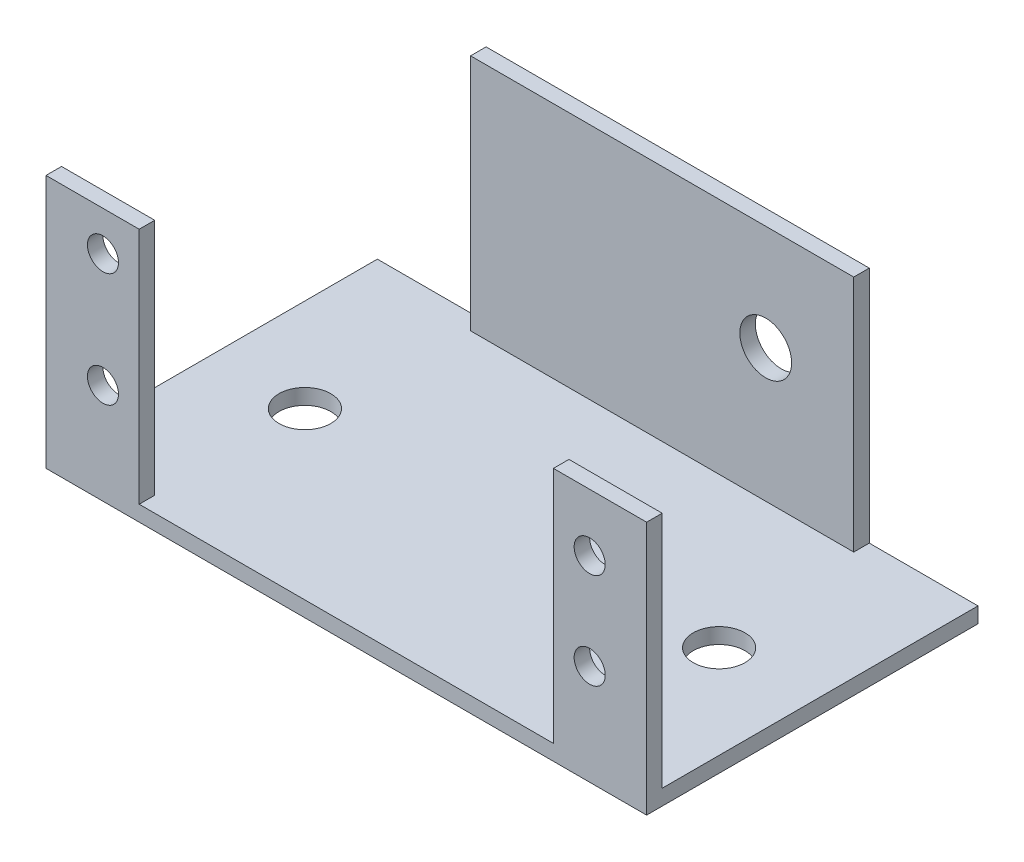
SolidWorks part; units mm, degrees
ref_plane "Front Plane" through (0, 0, 0) normal (0, 0, 1) x (1, 0, 0)
ref_plane "Top Plane" through (0, 0, 0) normal (0, 1, 0) x (1, 0, 0)
ref_plane "Right Plane" through (0, 0, 0) normal (1, 0, 0) x (0, 0, -1)
sketch "Sketch1" plane through (0, 0, 0) normal (0, 1, 0) x (1, 0, 0)
  line L0 (-29, -14.5) -> (29, -14.5)
  line L1 (29, 16) -> (-29, 16)
  line L2 (29, 16) -> (29, -16)
  line L3 (29, -16) -> (-29, -16)
  line L4 (-29, 16) -> (-29, -16)
  line L5 (29, 16) -> (-29, -16) construction
  line L6 (29, -16) -> (-29, 16) construction
  line L7 (-20, -14.5) -> (-20, -16)
  line L8 (20, -14.5) -> (20, -16)
  line L10 (18.5, 16) -> (-18.5, 16)
  line L11 (18.5, 16) -> (18.5, 14.5)
  line L12 (18.5, 14.5) -> (-18.5, 14.5)
  line L13 (-18.5, 16) -> (-18.5, 14.5)
  circle A0 centre (-20, 0) radius 2.5
  circle A1 centre (20, 0) radius 2.5
  point P0 (0, 0)
  point P16 (0, -14.5)
  point P21 (0, 14.5)
  point P22 (0, 0)
  dimension "D4" = 5
  dimension "D1" = 58
  dimension "D2" = 32
  dimension "D3" = 1.5
  dimension "D5" = 20
  dimension "D6" = 20
  dimension "D7" = 40
  dimension "D8" = 20
  dimension "D9" = 37
  dimension "D10" = 1.5
extrude "Boss-Extrude1" add sketch "Sketch1" against normal blind 1.5 contours L1 L4 L0 L2 A1 A0 | L0 L4 L3 L2 | L1 L13 L12 L11 | A0 | A1 | L2 L1 L4 L3 region at (0, 0, -0.2869) region at (0, 0, -15.25) region at (-20, 0, 0) region at (20, 0, 0)
extrude "Boss-Extrude2" add sketch "Sketch1<3>" along normal blind 23 contours L7 L0 L4 L3 | L0 L8 L3 L2 region at (-24.5, 0, 15.25) region at (24.5, 0, 15.25)
sketch "Sketch1<3>" plane through (0, 0, 0) normal (0, 1, 0) x (1, 0, 0) same geometry as "Sketch1"
sketch "Sketch2" plane through (0, 0, 16) normal (0, 0, 1) x (1, 0, 0)
  circle A0 centre (-23.5, 19.1975) radius 1.5
  circle A1 centre (-23.5, 8.1975) radius 1.5
  circle A2 centre (23.5, 17.4466) radius 1.5
  circle A3 centre (23.5, 8.1975) radius 1.5
  point P8 (0, 0)
  dimension "D4" = 3
  dimension "D1" = 11
  dimension "D2" = 47
  dimension "D3" = 23.5
extrude "Cut-Extrude1" cut sketch "Sketch2" against normal through all
extrude "Boss-Extrude3" add sketch "Sketch1<4>" along normal blind 23 contours L1 L13 L12 L11 region at (0, 0, -15.25)
sketch "Sketch1<4>" plane through (0, 0, 0) normal (0, 1, 0) x (1, 0, 0) same geometry as "Sketch1"
sketch "Sketch3" plane through (0, 0, -14.5) normal (0, 0, 1) x (1, 0, 0)
  line L0 (23.5, 17.4466) -> (23.5, 8.1975) construction
  circle A0 centre (10, 12.822) radius 2.5
  circle A1 centre (23.5, 17.4466) radius 1.5 construction
  point P8 (0, 0)
  point P9 (23.5, 12.822)
  dimension "D1" = 13.5
  dimension "D2" = 5
extrude "Cut-Extrude2" cut sketch "Sketch3" against normal through all
extrude "Cut-Extrude3" cut sketch "Sketch1<5>" against normal blind 25 contours A1 | A0 region at (20, 0, 0)
sketch "Sketch1<5>" plane through (0, 0, 0) normal (0, 1, 0) x (1, 0, 0) same geometry as "Sketch1"
